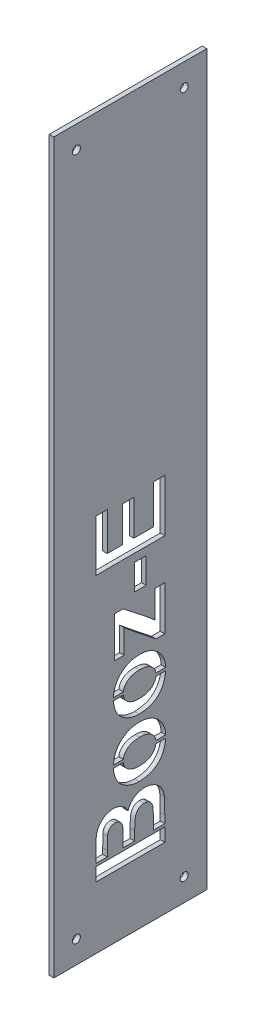
SolidWorks part; units mm, degrees
ref_plane "Front Plane" through (0, 0, 0) normal (1, 0, 0) x (0, 1, 0)
ref_plane "Top Plane" through (0, 0, 0) normal (0, 0, 1) x (0, 1, 0)
ref_plane "Right Plane" through (0, 0, 0) normal (0, 1, 0) x (-1, 0, 0)
sketch "Sketch1" plane through (0, 0, 0) normal (1, 0, 0) x (0, 1, 0)
  line L0 (0, 0) -> (0, 50) construction
  line L1 (-250, -50) -> (250, -50)
  line L2 (-250, -50) -> (-250, 50)
  line L3 (-250, 50) -> (250, 50)
  line L4 (250, -50) -> (250, 50)
  line L5 (-250, -50) -> (250, 50) construction
  line L6 (-250, 50) -> (250, -50) construction
  line L7 (0, 0) -> (250, 0) construction
  circle A0 centre (-237.5, 37.5) radius 2.8
  circle A1 centre (237.5, 37.5) radius 2.8
  circle A2 centre (237.5, -37.5) radius 2.8
  circle A3 centre (-237.5, -37.5) radius 2.8
  point P0 (0, 0)
  dimension "D3" = 5.6
  dimension "D1" = 500
  dimension "D2" = 100
  dimension "D4" = 12.5
  dimension "D5" = 12.5
extrude "Boss-Extrude1" add sketch "Sketch1" along normal blind 3.175
sketch "Sketch2" plane through (3.175, 0, 0) normal (1, 0, 0) x (0, 1, 0)
  line L1 (-215, -24) -> (-15, -24) construction
  line L2 (-250, 50) -> (-250, -50) construction
  line L3 (-250, -50) -> (250, -50) construction
  line L4 (-210.0769, 24) -> (-190.7404, 24)
  line L5 (-193.8269, -24) -> (-210.0769, -24)
  line L6 (-210.0769, -24) -> (-210.0769, 24)
  line L7 (-200.8462, 16) -> (-200.8462, 4.9231)
  line L8 (-200.8462, 4.9231) -> (-194.1635, 4.9231)
  line L9 (-194.9904, 16) -> (-200.8462, 16)
  line L10 (-200.8462, -3.0769) -> (-200.8462, -16)
  line L11 (-200.8462, -16) -> (-191.4231, -16)
  line L12 (-192.625, -3.0769) -> (-200.8462, -3.0769)
  line L13 (-84.5385, -24) -> (-84.5385, -17.8462)
  line L14 (-84.5385, -17.8462) -> (-71.4615, -1.4135)
  line L15 (-70.9423, 4.3077) -> (-83.3077, 4.3077)
  line L16 (-83.3077, 4.3077) -> (-83.3077, 11.0769)
  line L17 (-83.3077, 11.0769) -> (-55, 11.0769)
  line L18 (-55, 11.0769) -> (-55, 4.9231)
  line L19 (-55, 4.9231) -> (-68.2019, -11.7212)
  line L20 (-68.2019, -11.7212) -> (-72.8462, -17.2308)
  line L21 (-68.0769, -17.2308) -> (-53.7692, -17.2308)
  line L22 (-53.7692, -17.2308) -> (-53.7692, -24)
  line L23 (-53.7692, -24) -> (-84.5385, -24)
  line L24 (-48.8462, -11.0769) -> (-48.8462, -3.0769)
  line L25 (-48.8462, -3.0769) -> (-31, -3.0769)
  line L26 (-31, -3.0769) -> (-31, -11.0769)
  line L27 (-31, -11.0769) -> (-48.8462, -11.0769)
  line L28 (-25.4615, -24) -> (-25.4615, 24)
  line L29 (-25.4615, 24) -> (10.2308, 24)
  line L30 (10.2308, 24) -> (10.2308, 16)
  line L31 (10.2308, 16) -> (-16.2308, 16)
  line L32 (-16.2308, 16) -> (-16.2308, 5.5385)
  line L33 (-16.2308, 5.5385) -> (8.3846, 5.5385)
  line L34 (8.3846, 5.5385) -> (8.3846, -2.4615)
  line L35 (8.3846, -2.4615) -> (-16.2308, -2.4615)
  line L36 (-16.2308, -2.4615) -> (-16.2308, -16)
  line L37 (-16.2308, -16) -> (10.8462, -16)
  line L38 (10.8462, -16) -> (10.8462, -24)
  line L39 (10.8462, -24) -> (-25.4615, -24)
  spline S0 degree 3 poles (-190.7404, 24) (-189.8431, 23.9919) (-188.5411, 23.9936) (-186.8685, 23.9333) (-185.752, 23.8958) (-184.7307, 23.808) (-183.7967, 23.7391) (-182.9529, 23.6442) (-181.9589, 23.4907) (-180.8031, 23.2519) (-179.4976, 22.8102) (-178.2601, 22.2584) (-177.1092, 21.5569) (-176.0412, 20.7363) (-175.0477, 19.8034) (-174.1747, 18.7203) (-173.3884, 17.5382) (-172.7256, 16.2561) (-172.1049, 14.3937) (-171.9218, 12.9177) (-171.9231, 11.9231) knots 0 0 0 0 0.105884 0.153553 0.197457 0.237653 0.274456 0.307946 0.337788 0.393117 0.446926 0.500064 0.552657 0.605522 0.658748 0.713023 0.769236 0.826057 0.882736 1 1 1 1
  spline S1 degree 3 poles (-171.9231, 11.9231) (-171.9155, 10.833) (-172.1317, 9.2023) (-172.87, 7.1507) (-173.6413, 5.7146) (-174.588, 4.3977) (-176.0831, 2.8453) (-177.4471, 1.9611) (-178.4231, 1.5096) knots 0 0 0 0 0.252157 0.376787 0.502926 0.628342 0.751132 1 1 1 1
  spline S2 degree 3 poles (-178.4231, 1.5096) (-177.7772, 1.3002) (-176.8357, 0.9417) (-175.6704, 0.3103) (-174.866, -0.2057) (-174.114, -0.7754) (-173.4364, -1.4171) (-172.7943, -2.0946) (-172.2305, -2.8418) (-171.7202, -3.623) (-171.2871, -4.4503) (-170.912, -5.304) (-170.5983, -6.1925) (-170.3748, -7.122) (-170.1327, -8.4152) (-170.0906, -9.4161) (-170.0769, -10.0865) knots 0 0 0 0 0.132557 0.19578 0.258217 0.318868 0.379478 0.440087 0.500739 0.561785 0.621919 0.682673 0.743576 0.805446 0.868975 1 1 1 1
  spline S3 degree 3 poles (-170.0769, -10.0865) (-170.0834, -11.1686) (-170.2606, -12.8082) (-170.9097, -14.9153) (-171.5677, -16.4638) (-172.3861, -17.9239) (-173.3479, -19.257) (-174.4702, -20.4168) (-175.7129, -21.439) (-177.1134, -22.2845) (-179.2467, -23.1787) (-180.9892, -23.5476) (-182.1923, -23.6731) knots 0 0 0 0 0.162135 0.244884 0.329397 0.413636 0.495044 0.574817 0.654649 0.735398 0.818839 1 1 1 1
  spline S4 degree 3 poles (-182.1923, -23.6731) (-182.7364, -23.7214) (-183.6591, -23.7873) (-185.032, -23.8392) (-186.3779, -23.8903) (-187.939, -23.927) (-190.4455, -23.9631) (-192.4326, -23.9957) (-193.8269, -24) knots 0 0 0 0 0.140766 0.238316 0.354022 0.487867 0.640687 1 1 1 1
  spline S5 degree 3 poles (-194.1635, 4.9231) (-193.266, 4.9159) (-191.9904, 4.9303) (-190.3813, 4.9396) (-189.3844, 4.9576) (-188.5287, 4.9878) (-187.6726, 5.0228) (-187.1014, 5.0482) (-186.7692, 5.0865) knots 0 0 0 0 0.363929 0.517302 0.652498 0.76824 0.864499 1 1 1 1
  spline S6 degree 3 poles (-186.7692, 5.0865) (-185.973, 5.1885) (-184.8102, 5.424) (-183.4669, 6.1313) (-182.6346, 6.7653) (-181.9746, 7.5433) (-181.3096, 8.7665) (-181.1589, 9.8299) (-181.1538, 10.5385) knots 0 0 0 0 0.279181 0.403147 0.522445 0.638838 0.753413 1 1 1 1
  spline S7 degree 3 poles (-181.1538, 10.5385) (-181.1368, 11.2249) (-181.2996, 12.2287) (-181.8516, 13.4281) (-182.4344, 14.1807) (-183.1667, 14.816) (-184.4191, 15.511) (-185.5218, 15.7319) (-186.2788, 15.8365) knots 0 0 0 0 0.250586 0.366014 0.479792 0.596199 0.718553 1 1 1 1
  spline S8 degree 3 poles (-186.2788, 15.8365) (-186.6495, 15.8762) (-187.2944, 15.9005) (-188.2723, 15.9356) (-189.2723, 15.9656) (-190.4519, 15.9836) (-192.3782, 15.9927) (-193.9102, 16.0073) (-194.9904, 16) knots 0 0 0 0 0.12824 0.222081 0.336875 0.472602 0.628175 1 1 1 1
  spline S9 degree 3 poles (-191.4231, -16) (-190.5895, -16.0157) (-189.4007, -15.9833) (-187.9002, -15.9694) (-186.9615, -15.924) (-186.1503, -15.8894) (-185.3174, -15.8376) (-184.7612, -15.7567) (-184.4327, -15.7019) knots 0 0 0 0 0.356994 0.509418 0.64271 0.759541 0.857263 1 1 1 1
  spline S10 degree 3 poles (-184.4327, -15.7019) (-183.7154, -15.5867) (-182.6888, -15.2432) (-181.4822, -14.4977) (-180.7127, -13.7967) (-180.081, -12.9561) (-179.4483, -11.6021) (-179.3035, -10.4516) (-179.3077, -9.6731) knots 0 0 0 0 0.250408 0.369283 0.487615 0.607843 0.730168 1 1 1 1
  spline S11 degree 3 poles (-179.3077, -9.6731) (-179.3036, -8.9924) (-179.4271, -7.9906) (-179.9076, -6.7697) (-180.3943, -5.9661) (-181.0031, -5.2422) (-181.7554, -4.6364) (-182.6241, -4.1316) (-183.4522, -3.7991) (-184.2375, -3.5858) (-184.9865, -3.4458) (-185.8892, -3.3351) (-186.9412, -3.2414) (-188.1467, -3.1664) (-190.0567, -3.0833) (-191.5674, -3.0818) (-192.625, -3.0769) knots 0 0 0 0 0.120696 0.176255 0.231267 0.286442 0.342925 0.401446 0.463858 0.500356 0.545451 0.598688 0.661396 0.732508 0.81263 1 1 1 1
  spline S12 degree 3 poles (-164.5385, -5.9712) (-164.5254, -4.4553) (-164.2645, -2.1633) (-163.3084, 0.7683) (-162.507, 2.5607) (-161.7146, 3.931) (-161.0748, 4.9192) (-160.3606, 5.8331) (-159.5864, 6.6785) (-158.7699, 7.4758) (-157.8822, 8.1956) (-156.9347, 8.8503) (-155.9368, 9.4471) (-154.8899, 9.9711) (-153.8134, 10.4369) (-152.703, 10.8196) (-151.5663, 11.137) (-150.3985, 11.3913) (-148.783, 11.6173) (-147.5501, 11.6913) (-146.7212, 11.6923) knots 0 0 0 0 0.162141 0.244135 0.328745 0.371396 0.413193 0.454437 0.495169 0.53562 0.576273 0.617126 0.658595 0.700411 0.742144 0.783846 0.825811 0.868199 0.911452 1 1 1 1
  spline S13 degree 3 poles (-146.7212, 11.6923) (-145.466, 11.6938) (-143.6103, 11.5531) (-141.239, 11.0035) (-139.5791, 10.4426) (-138.0062, 9.7228) (-136.5284, 8.8284) (-135.1334, 7.7852) (-133.8476, 6.5871) (-132.6723, 5.2753) (-131.653, 3.857) (-130.783, 2.3598) (-130.0623, 0.7813) (-129.5161, -0.8869) (-129.0001, -3.2652) (-128.836, -5.1118) (-128.8462, -6.3654) knots 0 0 0 0 0.132301 0.195046 0.256021 0.316611 0.376898 0.437681 0.499809 0.561756 0.622956 0.68348 0.743929 0.805438 0.868034 1 1 1 1
  spline S14 degree 3 poles (-128.8462, -6.3654) (-128.8381, -7.6281) (-128.9948, -9.4927) (-129.5257, -11.8924) (-130.0831, -13.5774) (-130.8023, -15.1764) (-131.6685, -16.6947) (-132.7049, -18.1244) (-133.8915, -19.4505) (-135.1939, -20.6552) (-136.5789, -21.7261) (-138.0632, -22.609) (-139.6208, -23.3516) (-141.2676, -23.9143) (-143.6073, -24.4624) (-145.4289, -24.6275) (-146.6635, -24.6154) knots 0 0 0 0 0.132665 0.195844 0.257954 0.318876 0.379843 0.441369 0.504123 0.566581 0.627629 0.687774 0.747754 0.808695 0.870309 1 1 1 1
  spline S15 degree 3 poles (-146.6635, -24.6154) (-148.2249, -24.6159) (-150.5691, -24.3491) (-153.5749, -23.4408) (-155.3911, -22.6624) (-156.7784, -21.9022) (-157.7623, -21.2624) (-158.6902, -20.5758) (-159.5404, -19.807) (-160.3275, -18.9782) (-161.0621, -18.0974) (-161.7179, -17.1442) (-162.3132, -16.1359) (-162.8474, -15.0654) (-163.2928, -13.9297) (-163.6797, -12.7421) (-163.9989, -11.4999) (-164.2353, -10.1979) (-164.4702, -8.3534) (-164.535, -6.934) (-164.5385, -5.9712) knots 0 0 0 0 0.160512 0.240687 0.322168 0.363172 0.403209 0.442755 0.481727 0.520887 0.560212 0.599521 0.639706 0.68053 0.722388 0.765012 0.808893 0.854139 0.900982 1 1 1 1
  spline S16 degree 3 poles (-155.3077, -6.4615) (-155.3091, -7.3291) (-155.2385, -8.5961) (-154.9848, -10.2224) (-154.701, -11.3197) (-154.3585, -12.3439) (-153.9237, -13.2814) (-153.427, -14.15) (-152.8357, -14.917) (-152.1914, -15.596) (-151.516, -16.1993) (-150.803, -16.713) (-150.0481, -17.1308) (-149.252, -17.4476) (-148.1364, -17.7626) (-147.2595, -17.8407) (-146.6731, -17.8462) knots 0 0 0 0 0.162283 0.237015 0.307558 0.374125 0.438795 0.500611 0.560943 0.619487 0.675564 0.73015 0.783564 0.836573 0.890118 1 1 1 1
  spline S17 degree 3 poles (-146.6731, -17.8462) (-146.0864, -17.8412) (-145.2102, -17.7617) (-144.0964, -17.4497) (-143.3056, -17.1282) (-142.5525, -16.7134) (-141.84, -16.199) (-141.1651, -15.5985) (-140.526, -14.9158) (-139.9519, -14.1383) (-139.4503, -13.2725) (-139.0155, -12.3315) (-138.6714, -11.3018) (-138.4032, -10.1918) (-138.1431, -8.5519) (-138.0766, -7.271) (-138.0769, -6.3942) knots 0 0 0 0 0.109603 0.163012 0.215332 0.26861 0.323057 0.378992 0.436979 0.497276 0.558935 0.623441 0.690405 0.761205 0.836338 1 1 1 1
  spline S18 degree 3 poles (-138.0769, -6.3942) (-138.0773, -5.5368) (-138.1416, -4.2841) (-138.4058, -2.6772) (-138.6694, -1.5853) (-139.0173, -0.5695) (-139.453, 0.3608) (-139.9486, 1.2241) (-140.5294, 1.9935) (-141.1647, 2.6757) (-141.8401, 3.2758) (-142.5525, 3.7904) (-143.3056, 4.2051) (-144.0964, 4.5267) (-145.2102, 4.8386) (-146.0864, 4.9181) (-146.6731, 4.9231) knots 0 0 0 0 0.161387 0.235346 0.306138 0.372507 0.436992 0.499153 0.559459 0.617918 0.674309 0.7292 0.782913 0.835659 0.889503 1 1 1 1
  spline S19 degree 3 poles (-146.6731, 4.9231) (-147.2595, 4.9177) (-148.1364, 4.8395) (-149.252, 4.5245) (-150.0481, 4.2077) (-150.803, 3.79) (-151.516, 3.2763) (-152.1914, 2.6729) (-152.8357, 1.9939) (-153.427, 1.2269) (-153.9237, 0.3584) (-154.3585, -0.5791) (-154.701, -1.6034) (-154.9848, -2.7007) (-155.2385, -4.3269) (-155.3091, -5.594) (-155.3077, -6.4615) knots 0 0 0 0 0.109882 0.163427 0.216436 0.26985 0.324436 0.380513 0.439057 0.499389 0.561205 0.625875 0.692442 0.762985 0.837717 1 1 1 1
  spline S20 degree 3 poles (-123.9231, -5.9712) (-123.91, -4.4553) (-123.6492, -2.1633) (-122.693, 0.7683) (-121.8916, 2.5607) (-121.0992, 3.931) (-120.4594, 4.9192) (-119.7452, 5.8331) (-118.9711, 6.6785) (-118.1545, 7.4758) (-117.2668, 8.1956) (-116.3193, 8.8503) (-115.3215, 9.4471) (-114.2745, 9.9711) (-113.198, 10.4369) (-112.0876, 10.8196) (-110.9509, 11.137) (-109.7831, 11.3913) (-108.1676, 11.6173) (-106.9347, 11.6913) (-106.1058, 11.6923) knots 0 0 0 0 0.162141 0.244135 0.328745 0.371396 0.413193 0.454437 0.495169 0.53562 0.576273 0.617126 0.658595 0.700411 0.742144 0.783846 0.825811 0.868199 0.911452 1 1 1 1
  spline S21 degree 3 poles (-106.1058, 11.6923) (-104.8506, 11.6938) (-102.9949, 11.5531) (-100.6236, 11.0035) (-98.9637, 10.4426) (-97.3909, 9.7228) (-95.913, 8.8284) (-94.518, 7.7852) (-93.2322, 6.5871) (-92.0569, 5.2753) (-91.0376, 3.857) (-90.1677, 2.3598) (-89.4469, 0.7813) (-88.9007, -0.8869) (-88.3847, -3.2652) (-88.2206, -5.1118) (-88.2308, -6.3654) knots 0 0 0 0 0.132301 0.195046 0.256021 0.316611 0.376898 0.437681 0.499809 0.561756 0.622956 0.68348 0.743929 0.805438 0.868034 1 1 1 1
  spline S22 degree 3 poles (-88.2308, -6.3654) (-88.2227, -7.6281) (-88.3795, -9.4927) (-88.9103, -11.8924) (-89.4678, -13.5774) (-90.1869, -15.1764) (-91.0531, -16.6947) (-92.0895, -18.1244) (-93.2761, -19.4505) (-94.5786, -20.6552) (-95.9636, -21.7261) (-97.4478, -22.609) (-99.0054, -23.3516) (-100.6522, -23.9143) (-102.992, -24.4624) (-104.8135, -24.6275) (-106.0481, -24.6154) knots 0 0 0 0 0.132665 0.195844 0.257954 0.318876 0.379843 0.441369 0.504123 0.566581 0.627629 0.687774 0.747754 0.808695 0.870309 1 1 1 1
  spline S23 degree 3 poles (-106.0481, -24.6154) (-107.6095, -24.6159) (-109.9537, -24.3491) (-112.9595, -23.4408) (-114.7757, -22.6624) (-116.163, -21.9022) (-117.1469, -21.2624) (-118.0748, -20.5758) (-118.925, -19.807) (-119.7121, -18.9782) (-120.4467, -18.0974) (-121.1025, -17.1442) (-121.6978, -16.1359) (-122.232, -15.0654) (-122.6774, -13.9297) (-123.0643, -12.7421) (-123.3835, -11.4999) (-123.6199, -10.1979) (-123.8548, -8.3534) (-123.9196, -6.934) (-123.9231, -5.9712) knots 0 0 0 0 0.160512 0.240687 0.322168 0.363172 0.403209 0.442755 0.481727 0.520887 0.560212 0.599521 0.639706 0.68053 0.722388 0.765012 0.808893 0.854139 0.900982 1 1 1 1
  spline S24 degree 3 poles (-114.6923, -6.4615) (-114.6937, -7.3291) (-114.6231, -8.5961) (-114.3694, -10.2224) (-114.0856, -11.3197) (-113.7431, -12.3439) (-113.3084, -13.2814) (-112.8116, -14.15) (-112.2204, -14.917) (-111.576, -15.596) (-110.9006, -16.1993) (-110.1877, -16.713) (-109.4327, -17.1308) (-108.6367, -17.4476) (-107.521, -17.7626) (-106.6442, -17.8407) (-106.0577, -17.8462) knots 0 0 0 0 0.162283 0.237015 0.307558 0.374125 0.438795 0.500611 0.560943 0.619487 0.675564 0.73015 0.783564 0.836573 0.890118 1 1 1 1
  spline S25 degree 3 poles (-106.0577, -17.8462) (-105.471, -17.8412) (-104.5948, -17.7617) (-103.4811, -17.4497) (-102.6902, -17.1282) (-101.9372, -16.7134) (-101.2246, -16.199) (-100.5498, -15.5985) (-99.9106, -14.9158) (-99.3365, -14.1383) (-98.8349, -13.2725) (-98.4001, -12.3315) (-98.056, -11.3018) (-97.7878, -10.1918) (-97.5277, -8.5519) (-97.4612, -7.271) (-97.4615, -6.3942) knots 0 0 0 0 0.109603 0.163012 0.215332 0.26861 0.323057 0.378992 0.436979 0.497276 0.558935 0.623441 0.690405 0.761205 0.836338 1 1 1 1
  spline S26 degree 3 poles (-97.4615, -6.3942) (-97.4619, -5.5368) (-97.5263, -4.2841) (-97.7904, -2.6772) (-98.054, -1.5853) (-98.4019, -0.5695) (-98.8376, 0.3608) (-99.3332, 1.2241) (-99.914, 1.9935) (-100.5493, 2.6757) (-101.2247, 3.2758) (-101.9371, 3.7904) (-102.6902, 4.2051) (-103.4811, 4.5267) (-104.5948, 4.8386) (-105.471, 4.9181) (-106.0577, 4.9231) knots 0 0 0 0 0.161387 0.235346 0.306138 0.372507 0.436992 0.499153 0.559459 0.617918 0.674309 0.7292 0.782913 0.835659 0.889503 1 1 1 1
  spline S27 degree 3 poles (-106.0577, 4.9231) (-106.6442, 4.9177) (-107.521, 4.8395) (-108.6367, 4.5245) (-109.4327, 4.2077) (-110.1877, 3.79) (-110.9006, 3.2763) (-111.576, 2.6729) (-112.2204, 1.9939) (-112.8116, 1.2269) (-113.3084, 0.3584) (-113.7431, -0.5791) (-114.0856, -1.6034) (-114.3694, -2.7007) (-114.6231, -4.3269) (-114.6937, -5.594) (-114.6923, -6.4615) knots 0 0 0 0 0.109882 0.163427 0.216436 0.26985 0.324436 0.380513 0.439057 0.499389 0.561205 0.625875 0.692442 0.762985 0.837717 1 1 1 1
  spline S28 degree 3 poles (-71.4615, -1.4135) (-70.9687, -0.7833) (-70.229, 0.1043) (-69.301, 1.2583) (-68.671, 2.0047) (-68.1085, 2.6909) (-67.4537, 3.4498) (-66.9892, 3.9822) (-66.6923, 4.3077) knots 0 0 0 0 0.322142 0.465273 0.59633 0.715487 0.822591 1 1 1 1
  spline S29 degree 3 poles (-66.6923, 4.3077) (-67.3141, 4.3077) (-68.7308, 4.3077) (-70.1474, 4.3077) (-70.9423, 4.3077) knots 0 0 0 0 0.438914 1 1 1 1
  spline S30 degree 3 poles (-72.8462, -17.2308) (-72.266, -17.2308) (-71.4423, -17.2308) (-70.4038, -17.2308) (-69.7628, -17.2308) (-69.2115, -17.2308) (-68.6603, -17.2308) (-68.2917, -17.2308) (-68.0769, -17.2308) knots 0 0 0 0 0.364919 0.518145 0.653226 0.768145 0.864919 1 1 1 1
  dimension "D1" = 35
  dimension "D2" = 26
  dimension "D3" = 200
extrude "Cut-Extrude1" cut sketch "Sketch2" against normal through all
sketch "Sketch3" plane through (3.175, 0, 0) normal (1, 0, 0) x (0, 1, 0)
  line L1 (-200.8462, 24) -> (-198.8462, 24)
  line L2 (-200.8462, 24) -> (-200.8462, -24)
  line L3 (-200.8462, -24) -> (-198.8462, -24)
  line L4 (-198.8462, 24) -> (-198.8462, -24)
  line L5 (-200.8462, 24) -> (-198.8462, -24) construction
  line L6 (-200.8462, -24) -> (-198.8462, 24) construction
  line L7 (-210.0769, -24) -> (-193.8269, -24) construction
  line L8 (-146.6731, -6.4643) -> (-146.6731, 4.9231) construction
  line L9 (-147.6731, 11.67) -> (-145.6731, 11.67)
  line L10 (-147.6731, 11.67) -> (-147.6731, -24.5987)
  line L11 (-147.6731, -24.5987) -> (-145.6731, -24.5987)
  line L12 (-145.6731, 11.67) -> (-145.6731, -24.5987)
  line L13 (-147.6731, 11.67) -> (-145.6731, -24.5987) construction
  line L14 (-147.6731, -24.5987) -> (-145.6731, 11.67) construction
  line L15 (-105.0577, 11.6704) -> (-107.0577, 11.6704)
  line L16 (-105.0577, 11.6704) -> (-105.0577, -24.5908)
  line L17 (-105.0577, -24.5908) -> (-107.0577, -24.5908)
  line L18 (-107.0577, 11.6704) -> (-107.0577, -24.5908)
  line L19 (-105.0577, 11.6704) -> (-107.0577, -24.5908) construction
  line L20 (-105.0577, -24.5908) -> (-107.0577, 11.6704) construction
  line L21 (-106.0577, -6.4602) -> (-106.0577, 4.9231) construction
  line L22 (-200.8462, 16) -> (-200.8462, 4.9231) construction
  line L23 (-190.7404, 24) -> (-210.0769, 24) construction
  line L25 (-147.6731, 18.4765) -> (-145.6731, 18.4765)
  line L26 (-147.6731, 18.4765) -> (-147.6731, 4.8635)
  line L27 (-147.6731, 4.8635) -> (-145.6731, 4.8635)
  line L28 (-145.6731, 18.4765) -> (-145.6731, 4.8635)
  line L29 (-147.6731, 18.4765) -> (-145.6731, 4.8635) construction
  line L30 (-147.6731, 4.8635) -> (-145.6731, 18.4765) construction
  line L31 (-147.6731, -31.4108) -> (-145.6731, -31.4108)
  line L32 (-147.6731, -31.4108) -> (-147.6731, -17.7866)
  line L33 (-147.6731, -17.7866) -> (-145.6731, -17.7866)
  line L34 (-145.6731, -31.4108) -> (-145.6731, -17.7866)
  line L35 (-147.6731, -31.4108) -> (-145.6731, -17.7866) construction
  line L36 (-147.6731, -17.7866) -> (-145.6731, -31.4108) construction
  line L37 (-107.0577, -31.395) -> (-105.0577, -31.395)
  line L38 (-107.0577, -31.395) -> (-107.0577, -17.7866)
  line L39 (-107.0577, -17.7866) -> (-105.0577, -17.7866)
  line L40 (-105.0577, -31.395) -> (-105.0577, -17.7866)
  line L41 (-107.0577, -31.395) -> (-105.0577, -17.7866) construction
  line L42 (-107.0577, -17.7866) -> (-105.0577, -31.395) construction
  line L43 (-107.0577, -2.939) -> (-105.0577, -2.939)
  line L44 (-107.0577, -2.939) -> (-107.0577, 12.7852)
  line L45 (-107.0577, 12.7852) -> (-105.0577, 12.7852)
  line L46 (-105.0577, -2.939) -> (-105.0577, 12.7852)
  line L47 (-107.0577, -2.939) -> (-105.0577, 12.7852) construction
  line L48 (-107.0577, 12.7852) -> (-105.0577, -2.939) construction
  circle A0 centre (-146.6731, 11.67) radius 1
  circle A1 centre (-146.6731, -24.5987) radius 1
  circle A2 centre (-106.0577, -24.5908) radius 1
  circle A3 centre (-106.0577, 11.6704) radius 1
  spline S0 degree 3 poles (-146.7212, 11.6923) (-147.5501, 11.6913) (-148.783, 11.6173) (-150.3985, 11.3913) (-151.5663, 11.137) (-152.703, 10.8196) (-153.8134, 10.4369) (-154.8899, 9.9711) (-155.9368, 9.4471) (-156.9347, 8.8503) (-157.8822, 8.1956) (-158.7699, 7.4758) (-159.5864, 6.6785) (-160.3606, 5.8331) (-161.0748, 4.9192) (-161.7146, 3.931) (-162.507, 2.5607) (-163.3084, 0.7683) (-164.2645, -2.1633) (-164.5254, -4.4553) (-164.5385, -5.9712) knots 0 0 0 0 0.088548 0.131801 0.174189 0.216154 0.257856 0.299589 0.341405 0.382874 0.423727 0.46438 0.504831 0.545563 0.586807 0.628604 0.671255 0.755865 0.837859 1 1 1 1 construction
  spline S1 degree 3 poles (-146.6635, -24.6154) (-145.4289, -24.6275) (-143.6073, -24.4624) (-141.2676, -23.9143) (-139.6208, -23.3516) (-138.0632, -22.609) (-136.5789, -21.7261) (-135.1939, -20.6552) (-133.8915, -19.4505) (-132.7049, -18.1244) (-131.6685, -16.6947) (-130.8023, -15.1764) (-130.0831, -13.5774) (-129.5257, -11.8924) (-128.9948, -9.4927) (-128.8381, -7.6281) (-128.8462, -6.3654) knots 0 0 0 0 0.129691 0.191305 0.252246 0.312226 0.372371 0.433419 0.495877 0.558631 0.620157 0.681124 0.742046 0.804156 0.867335 1 1 1 1 construction
  spline S2 degree 3 poles (-88.2308, -6.3654) (-88.2206, -5.1118) (-88.3847, -3.2652) (-88.9007, -0.8869) (-89.4469, 0.7813) (-90.1677, 2.3598) (-91.0376, 3.857) (-92.0569, 5.2753) (-93.2322, 6.5871) (-94.518, 7.7852) (-95.913, 8.8284) (-97.3909, 9.7228) (-98.9637, 10.4426) (-100.6236, 11.0035) (-102.9949, 11.5531) (-104.8506, 11.6938) (-106.1058, 11.6923) knots 0 0 0 0 0.131966 0.194562 0.256071 0.31652 0.377044 0.438244 0.500191 0.562319 0.623102 0.683389 0.743979 0.804954 0.867699 1 1 1 1 construction
  spline S3 degree 3 poles (-123.9231, -5.9712) (-123.9196, -6.934) (-123.8548, -8.3534) (-123.6199, -10.1979) (-123.3835, -11.4999) (-123.0643, -12.7421) (-122.6774, -13.9297) (-122.232, -15.0654) (-121.6978, -16.1359) (-121.1025, -17.1442) (-120.4467, -18.0974) (-119.7121, -18.9782) (-118.925, -19.807) (-118.0748, -20.5758) (-117.1469, -21.2624) (-116.163, -21.9022) (-114.7757, -22.6624) (-112.9595, -23.4408) (-109.9537, -24.3491) (-107.6095, -24.6159) (-106.0481, -24.6154) knots 0 0 0 0 0.099018 0.145861 0.191107 0.234988 0.277612 0.31947 0.360294 0.400479 0.439788 0.479113 0.518273 0.557245 0.596791 0.636828 0.677832 0.759313 0.839488 1 1 1 1 construction
  spline S4 degree 3 poles (-138.0769, -6.3942) (-138.0773, -5.5368) (-138.1416, -4.2841) (-138.4058, -2.6772) (-138.6694, -1.5853) (-139.0173, -0.5695) (-139.453, 0.3608) (-139.9486, 1.2241) (-140.5294, 1.9935) (-141.1647, 2.6757) (-141.8401, 3.2758) (-142.5525, 3.7904) (-143.3056, 4.2051) (-144.0964, 4.5267) (-145.2102, 4.8386) (-146.0864, 4.9181) (-146.6731, 4.9231) knots 0 0 0 0 0.161387 0.235346 0.306138 0.372507 0.436992 0.499153 0.559459 0.617918 0.674309 0.7292 0.782913 0.835659 0.889503 1 1 1 1 construction
  spline S5 degree 3 poles (-146.6731, -17.8462) (-146.0864, -17.8412) (-145.2102, -17.7617) (-144.0964, -17.4497) (-143.3056, -17.1282) (-142.5525, -16.7134) (-141.84, -16.199) (-141.1651, -15.5985) (-140.526, -14.9158) (-139.9519, -14.1383) (-139.4503, -13.2725) (-139.0155, -12.3315) (-138.6714, -11.3018) (-138.4032, -10.1918) (-138.1431, -8.5519) (-138.0766, -7.271) (-138.0769, -6.3942) knots 0 0 0 0 0.109603 0.163012 0.215332 0.26861 0.323057 0.378992 0.436979 0.497276 0.558935 0.623441 0.690405 0.761205 0.836338 1 1 1 1 construction
  spline S6 degree 3 poles (-106.0577, -17.8462) (-105.471, -17.8412) (-104.5948, -17.7617) (-103.4811, -17.4497) (-102.6902, -17.1282) (-101.9372, -16.7134) (-101.2246, -16.199) (-100.5498, -15.5985) (-99.9106, -14.9158) (-99.3365, -14.1383) (-98.8349, -13.2725) (-98.4001, -12.3315) (-98.056, -11.3018) (-97.7878, -10.1918) (-97.5277, -8.5519) (-97.4612, -7.271) (-97.4615, -6.3942) knots 0 0 0 0 0.109603 0.163012 0.215332 0.26861 0.323057 0.378992 0.436979 0.497276 0.558935 0.623441 0.690405 0.761205 0.836338 1 1 1 1 construction
  point P4 (-199.8462, 0)
  point P13 (-146.6731, -6.4643)
  point P22 (-106.0577, -6.4602)
  dimension "D1" = 0
  dimension "D2" = 2
  dimension "D3" = 2
  dimension "D4" = 2
extrude "Boss-Extrude4" add sketch "Sketch3" against normal through all contours L4 L1 L2 L3 | L11 A1 | L11 A1 | A1 L12 A0 L10 | L9 A0 | L9 A0 | L15 A3 | L15 A3 | L17 A2 | L17 A2 | A3 L18 A2 L16 | A3 L18 L43 L16 | A2 L16 L39 L18 | A2 L38 L37 L40 | A1 L32 L31 L34 | A0 L28 L25 L26 | A0 L10 L27 L12 | A1 L12 L33 L10 region at (3.175, -199.8462, 0) region at (3.175, -146.6731, 12.0944) region at (3.175, -146.6731, 7.8782) region at (3.175, -146.6731, 15.4618) region at (3.175, -146.6731, 11.2456) region at (3.175, -146.6731, -20.804) region at (3.175, -146.6731, -24.1742) region at (3.175, -146.6731, -28.3933) region at (3.175, -146.6731, -25.0231) region at (3.175, -106.0577, 11.246) region at (3.175, -106.0577, 12.6933) region at (3.175, -106.0577, 12.0948) region at (3.175, -106.0577, 3.9748) region at (3.175, -106.0577, -20.8001) region at (3.175, -106.0577, -25.0152) region at (3.175, -106.0577, -24.1664) region at (3.175, -106.0577, -28.3815)
sketch "Sketch9" plane through (3.175, 0, 0) normal (1, 0, 0) x (0, 1, 0)
  line L1 (-253.175, 53.175) -> (253.175, 53.175)
  line L2 (-253.175, 53.175) -> (-253.175, -53.175)
  line L3 (-253.175, -53.175) -> (253.175, -53.175)
  line L4 (253.175, 53.175) -> (253.175, -53.175)
  line L5 (-253.175, 53.175) -> (253.175, -53.175) construction
  line L6 (-253.175, -53.175) -> (253.175, 53.175) construction
  line L7 (-250, 50) -> (250, 50)
  line L8 (-250, 50) -> (-250, -50)
  line L9 (-250, -50) -> (250, -50)
  line L10 (250, 50) -> (250, -50)
  line L11 (-250, 50) -> (250, -50) construction
  line L12 (-250, -50) -> (250, 50) construction
  point P4 (0, 0)
  point P9 (0, 0)
  dimension "D1" = 3.175
  dimension "D2" = 3.175
  dimension "D3" = 3.175
  dimension "D4" = 3.175
extrude "Boss-Extrude5" add sketch "Sketch9" against normal through all contours L4 L1 L2 L3 L7 L10 L9 L8 region at (3.175, 0, 52.6576)
